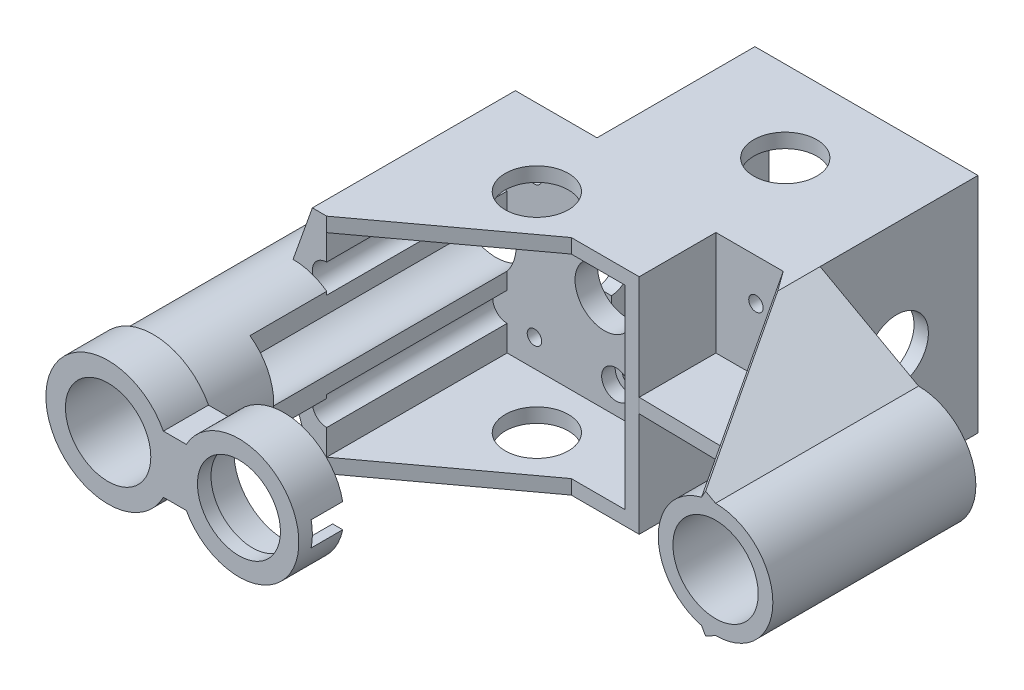
SolidWorks part; units mm, degrees
ref_plane "Front" through (0, 0, 0) normal (0, 0, 1) x (1, 0, 0)
ref_plane "Top" through (0, 0, 0) normal (0, 1, 0) x (1, 0, 0)
ref_plane "Right" through (0, 0, 0) normal (1, 0, 0) x (0, 0, -1)
sketch "Sketch4" plane through (0, 0, 0) normal (0, 0, 1) x (1, 0, 0)
  line L0 (0, -42.8625) -> (0, 41.275) construction
  line L1 (-49.15, -15.5) -> (-80.15, 15.5) construction
  line L2 (-80.15, -15.5) -> (-49.15, 15.5) construction
  line L3 (-39.925, 44.5615) -> (-39.925, -66.5635) construction
  line L4 (-71.275, 44.5615) -> (-71.275, -66.5635) construction
  line L8 (-62.05, 15.5) -> (-31.05, -15.5) construction
  line L9 (-31.05, 15.5) -> (-62.05, -15.5) construction
  line L11 (-31.05, 36.624) -> (-31.05, -53.8635) construction
  line L12 (43.75, 0) -> (-164.4633, 0) construction
  line L13 (-62.05, 36.624) -> (-62.05, -53.8635) construction
  line L14 (-49.15, 36.624) -> (-49.15, -53.8635) construction
  line L15 (-80.15, 36.624) -> (-80.15, -53.8635) construction
  line L16 (-113.2228, 15.5) -> (-0.2036, 15.5) construction
  line L17 (-113.2228, -15.5) -> (-0.2036, -15.5) construction
  line L18 (-25, -66.5635) -> (-25, 44.5615) construction
  line L19 (-68.1, -66.5635) -> (-68.1, 44.5615) construction
  line L20 (-43.1, 44.5615) -> (-43.1, -66.5635) construction
  line L21 (-86.2, -66.5635) -> (-86.2, 44.5615) construction
  line L22 (5.8397, -21.55) -> (-134.1626, -21.55) construction
  line L23 (5.8397, 21.55) -> (-134.1626, 21.55) construction
  line L24 (10.9249, -24.725) -> (-138.6228, -24.725) construction
  line L25 (10.9249, 24.725) -> (-138.6228, 24.725) construction
  line L26 (-89.375, 44.5615) -> (-89.375, -66.5635) construction
  line L27 (-21.825, 44.5615) -> (-21.825, -66.5635) construction
  circle A0 centre (0, 0) radius 12.7 construction
  circle A1 centre (0, 0) radius 15.875 construction
  circle A2 centre (0, 0) radius 9.46 construction
  circle A3 centre (-93.65, 0) radius 9.46 construction
  arc A4 (-93.65, 12.7) -> (-93.65, -12.7) centre (-93.65, 0) ccw construction
  circle A5 centre (27.27, 0) radius 9.46 construction
  circle A6 centre (27.27, 0) radius 12.7 construction
  circle A7 centre (-120.3675, 0) radius 9.46 construction
  circle A8 centre (-120.3675, 0) radius 12.7 construction
  point P3 (0, 0)
  point P6 (-49.15, -15.5)
  point P11 (-93.65, 0)
  point P12 (-49.15, 15.5)
  point P13 (-46.55, 0)
  point P14 (-80.15, 15.5)
  point P15 (-80.15, -15.5)
  point P61 (-64.65, 0)
  point P65 (27.27, 0)
  point P66 (-120.3675, 0)
  dimension "D20" = 3.175
  dimension "D18" = 29
  dimension "D26" = 73.82
  dimension "D27" = 64.65
  dimension "D2" = 31
  dimension "D3" = 25
  dimension "D4" = 31
  dimension "D5" = 21.825
  dimension "D6" = 15.5
  dimension "D7" = 15.5
  dimension "D8" = 6.05
  dimension "D9" = 6.05
  dimension "D10" = 6.05
  dimension "D11" = 6.05
  dimension "D12" = 6.05
  dimension "D13" = 6.05
  dimension "D14" = 3.175
  dimension "D15" = 3.175
  dimension "D16" = 3.175
  dimension "D17" = 3.175
  dimension "D19" = 3.175
  dimension "D21" = 3.175
  dimension "D22" = 46.55
  dimension "D23" = 47.1
  dimension "D24" = 58.32
  dimension "D25" = 147.6375
sketch "Sketch5" plane through (0, 0, 0) normal (0, 0, 1) x (1, 0, 0)
  line L0 (-21.825, -24.725) -> (0, -12.7)
  line L1 (10.9249, -24.725) -> (-138.6228, -24.725) construction
  line L2 (-21.825, 44.5615) -> (-21.825, -66.5635) construction
  line L3 (0, -42.8625) -> (0, 41.275) construction
  line L4 (10.9249, 24.725) -> (-138.6228, 24.725) construction
  line L5 (-21.825, 24.725) -> (0, 12.7)
  line L6 (-93.65, 0) -> (-93.65, -30.9694) construction
  line L7 (-93.65, 12.7) -> (-89.375, 24.725)
  line L8 (-89.375, 44.5615) -> (-89.375, -66.5635) construction
  line L9 (-89.375, 24.725) -> (-21.825, 24.725)
  line L10 (-89.375, -24.725) -> (-93.65, -12.7)
  line L11 (-89.375, -24.725) -> (-21.825, -24.725)
  circle A0 centre (0, 0) radius 12.7 construction
  arc A1 (0, 12.7) -> (0, -12.7) centre (0, 0) cw
  circle A2 centre (0, 0) radius 9.46
  circle A3 centre (-93.65, 0) radius 9.46
  arc A4 (-93.65, 12.7) -> (-93.65, -12.7) centre (-93.65, 0) ccw
  circle A6 centre (-31.05, 15.5) radius 1.6
  circle A7 centre (-31.05, -15.5) radius 1.6
  circle A8 centre (-49.15, -15.5) radius 1.6
  circle A9 centre (-49.15, 15.5) radius 1.6
  circle A10 centre (-62.05, 15.5) radius 1.6
  circle A11 centre (-80.15, 15.5) radius 1.6
  circle A12 centre (-80.15, -15.5) radius 1.6
  circle A13 centre (-62.05, -15.5) radius 1.6
extrude "Extrude1" add sketch "Sketch5" along normal blind 5
sketch "Sketch6" plane through (0, 0, 5) normal (0, 0, 1) x (1, 0, 0)
  line L0 (-86.2, -21.55) -> (-43.1, -21.55)
  line L1 (-86.2, -66.5635) -> (-86.2, 44.5615) construction
  line L2 (5.8397, -21.55) -> (-134.1626, -21.55) construction
  line L3 (-43.1, 44.5615) -> (-43.1, -66.5635) construction
  line L4 (-43.1, -21.55) -> (-43.1, 21.55)
  line L5 (5.8397, 21.55) -> (-134.1626, 21.55) construction
  line L6 (-43.1, 21.55) -> (-86.2, 21.55)
  line L7 (-39.925, 24.725) -> (-89.375, 24.725)
  line L8 (-93.65, -12.7) -> (-89.375, -24.725) construction
  line L9 (-39.925, 44.5615) -> (-39.925, -66.5635) construction
  line L10 (10.9249, 24.725) -> (-138.6228, 24.725) construction
  line L11 (-12.601, 1.5825) -> (-39.925, 1.5825)
  line L12 (-39.925, -24.725) -> (-89.375, -24.725)
  line L13 (-86.2, 21.55) -> (-86.2, 15.8916)
  line L14 (-86.2, -9.5084) -> (-86.2, -5.83)
  line L15 (-89.375, -24.725) -> (-93.65, -12.7)
  line L16 (-89.375, 24.725) -> (-93.65, 12.7)
  line L19 (-86.2, 9.5416) -> (-86.2, 5.83)
  line L20 (-86.2, -21.55) -> (-86.2, -15.8584)
  line L24 (-39.925, -1.5851) -> (-12.6007, -1.5851)
  line L25 (-39.925, 1.5825) -> (-39.925, 24.725)
  line L27 (-21.825, -24.725) -> (0, -12.7)
  line L28 (-21.825, 24.725) -> (0, 12.7)
  line L29 (-25, 24.725) -> (-3.1127, 12.3127)
  line L30 (-25, -66.5635) -> (-25, 44.5615) construction
  line L31 (-25, -24.725) -> (-3.1127, -12.3127)
  line L32 (10.9249, -24.725) -> (-138.6228, -24.725) construction
  line L33 (-25, -24.725) -> (-21.825, -24.725)
  line L34 (-39.925, -1.5851) -> (-39.925, -24.725)
  line L35 (-25, 24.725) -> (-21.825, 24.725)
  line L36 (0, -42.8625) -> (0, 41.275) construction
  circle A0 centre (-93.65, 0) radius 9.46 construction
  arc A1 (-93.65, 12.7) -> (-93.65, -12.7) centre (-93.65, 0) ccw
  arc A3 (-86.2, 5.83) -> (-86.2, -5.83) centre (-93.65, 0) ccw
  circle A4 centre (0, 0) radius 9.46
  circle A5 centre (0, 0) radius 12.7 construction
  arc A6 (0, -12.7) -> (0, 12.7) centre (0, 0) ccw
  arc A7 (-3.1127, 12.3127) -> (-12.601, 1.5825) centre (0, 0) ccw
  arc A8 (-3.1127, -12.3127) -> (-12.6007, -1.5851) centre (0, 0) cw
  circle A13 centre (-86.2, 12.7166) radius 3.175 construction
  circle A14 centre (-86.2, -12.6834) radius 3.175 construction
  arc A15 (-86.2, 15.8916) -> (-86.2, 9.5416) centre (-86.2, 12.7166) ccw
  arc A16 (-86.2, -9.5084) -> (-86.2, -15.8584) centre (-86.2, -12.6834) ccw
  point P36 (-86.2, 12.7166)
  point P39 (-86.2, -12.6834)
extrude "Extrude2" add sketch "Sketch6" along normal blind 40
sketch "Sketch7" plane through (0, 0, 0) normal (0, 0, -1) x (-1, 0, 0)
  line L0 (68.1, 21.55) -> (25, 21.55)
  line L1 (25, -66.5635) -> (25, 44.5615) construction
  line L2 (-5.8397, -21.55) -> (134.1626, -21.55) construction
  line L3 (25, 21.55) -> (25, -21.55)
  line L4 (68.1, -66.5635) -> (68.1, 44.5615) construction
  line L5 (-5.8397, 21.55) -> (134.1626, 21.55) construction
  line L6 (68.1, 21.55) -> (68.1, -21.55)
  line L7 (68.1, -21.55) -> (25, -21.55)
  line L8 (21.825, 24.725) -> (21.825, -24.725)
  line L9 (21.825, 24.725) -> (71.275, 24.725)
  line L10 (71.275, 44.5615) -> (71.275, -66.5635) construction
  line L11 (-10.9249, 24.725) -> (138.6228, 24.725) construction
  line L12 (71.275, 24.725) -> (71.275, -24.725)
  line L13 (-10.9249, -24.725) -> (138.6228, -24.725) construction
  line L14 (71.275, -24.725) -> (21.825, -24.725)
extrude "Extrude3" add sketch "Sketch7" along normal blind 35
sketch "Sketch12" plane through (4.5259, 7.9808, 0) normal (-0.4933, -0.8699, 0) x (0, 0, 1)
  line L0 (45, 8.7814) -> (5, 33.9433)
  line L1 (5, 33.9433) -> (45, 33.9433)
  line L2 (45, 33.9433) -> (45, 8.7814)
extrude "Extrude5" cut sketch "Sketch12" against normal up to surface (1.5323 mm away) up to face at (-10.9125, 18.7125, 22.5)
sketch "Sketch13" plane through (4.5259, -7.9808, 0) normal (-0.4933, 0.8699, 0) x (0, 0, 1)
  line L0 (45, -8.7814) -> (5, -33.9433)
  line L1 (5, -33.9433) -> (45, -33.9433)
  line L2 (45, -33.9433) -> (45, -8.7814)
extrude "Extrude6" cut sketch "Sketch13" against normal up to surface (1.5323 mm away) up to face at (-10.9125, -18.7125, 22.5)
sketch "Sketch16" plane through (0, -24.725, 0) normal (0, -1, 0) x (1, 0, 0)
  line L0 (-39.925, 5) -> (-39.925, 22) construction
  line L1 (-39.925, 45) -> (-39.925, 5) construction
  line L2 (-39.925, 22) -> (-16.782, 22.4034)
  line L3 (-16.782, 22.4034) -> (-12.6007, 29.0539)
  line L4 (-12.6007, 45) -> (-12.6007, 5) construction
  line L5 (-12.6007, 29.0539) -> (-12.6007, 45)
  line L6 (-12.6007, 45) -> (-86.2, 45)
  line L7 (-86.2, 45) -> (-54.9816, 22)
  line L8 (-54.9816, 22) -> (-39.925, 22)
  line L9 (-46.55, 0) -> (-46.55, -39.1338) construction
  line L10 (-67.6181, 0) -> (-67.6181, 27.6964) construction
  line L11 (10.9249, 0) -> (-138.6228, 0) construction
  circle A0 centre (-46.55, -17) radius 7
  circle A1 centre (-67.6181, 17) radius 7
extrude "Extrude9" cut sketch "Sketch16" against normal up to surface (49.45 mm away) up to face at (-47.67, 24.725, 3.9695)
sketch "Sketch17" plane through (0, 0, 45) normal (0, 0, 1) x (1, 0, 0)
  line L1 (-86.2, -66.5635) -> (-86.2, 44.5615) construction
  line L2 (-86.2, 10.2853) -> (-86.2, 5.83)
  line L3 (-86.2, -5.83) -> (-86.2, -10.2853)
  arc A0 (-86.2, 5.83) -> (-86.2, -5.83) centre (-93.65, 0) ccw
  arc A1 (-93.65, 12.7) -> (-92.406, -12.6389) centre (-93.65, 0) ccw
  arc A2 (-93.65, 12.7) -> (-93.65, -12.7) centre (-93.65, 0) ccw construction
  arc A3 (-92.406, -12.6389) -> (-86.2, -10.2853) centre (-93.65, 0) ccw
  arc A4 (-93.65, 12.7) -> (-86.2, 10.2853) centre (-93.65, 0) cw
extrude "Extrude10" add sketch "Sketch17" along normal blind 17
sketch "Sketch18" plane through (0, 0, 62) normal (0, 0, 1) x (1, 0, 0)
  circle A0 centre (-93.65, 0) radius 9.46
  circle A1 centre (-93.65, 0) radius 12.7
extrude "Extrude11" add sketch "Sketch18" along normal blind 14
sketch "Sketch19" plane through (0, 0, 76) normal (0, 0, 1) x (1, 0, 0)
  line L0 (-81.3983, -6.3446) -> (-76.3158, -6.3446)
  line L1 (-81.3983, 6.3446) -> (-76.3158, 6.3446)
  circle A0 centre (-64.65, 0) radius 11.1
  circle A1 centre (-64.65, 0) radius 13.2795 construction
  circle A2 centre (-93.65, 0) radius 9.46
  circle A3 centre (-93.65, 0) radius 13.797 construction
  arc A4 (-76.3158, -6.3446) -> (-76.3158, 6.3446) centre (-64.65, 0) ccw
  arc A5 (-81.3983, 6.3446) -> (-81.3983, -6.3446) centre (-93.65, 0) ccw
extrude "Extrude12" add sketch "Sketch19" along normal blind 7
sketch "Sketch20" plane through (0, 0, 83) normal (0, 0, 1) x (1, 0, 0)
  line L1 (-81.3983, -6.3446) -> (-76.3158, -6.3446) construction
  line L2 (-81.3983, -6.3446) -> (-76.3158, -6.3446)
  line L3 (-81.3983, 6.3446) -> (-76.3158, 6.3446)
  circle A0 centre (-93.65, 0) radius 9.46
  circle A1 centre (-93.65, 0) radius 12.7 construction
  circle A2 centre (-64.65, 0) radius 14.39 construction
  arc A3 (-81.3983, 6.3446) -> (-81.3983, -6.3446) centre (-93.65, 0) ccw
  arc A4 (-76.3158, -6.3446) -> (-76.3158, 6.3446) centre (-64.65, 0) ccw
  circle A5 centre (-64.65, 0) radius 9.2
extrude "Extrude13" add sketch "Sketch20" along normal blind 3
sketch "Sketch21" plane through (-43.1, 0, 0) normal (-1, 0, 0) x (0, 0, 1)
  line L0 (76, 0) -> (76, -2.7)
  line L1 (76, 13.797) -> (76, -13.797) construction
  line L2 (76, 0) -> (76, 2.7)
  line L3 (76, -2.7) -> (83, -2.7)
  line L4 (83, 11.1) -> (83, -11.1) construction
  line L5 (83, -2.7) -> (83, 2.7)
  line L6 (83, 2.7) -> (76, 2.7)
extrude "Extrude14" cut sketch "Sketch21" along normal blind 15
sketch "Sketch22" plane through (0, 0, 5) normal (0, 0, 1) x (1, 0, 0)
  circle A0 centre (-62.05, 15.5) radius 3.2
  circle A1 centre (-62.05, -15.5) radius 3.2
extrude "Extrude15" cut sketch "Sketch22" against normal blind 3
sketch "Sketch23" plane through (0, 0, 0) normal (0, 0, -1) x (-1, 0, 0)
  circle A0 centre (49.15, 15.5) radius 3.2
  circle A1 centre (49.15, -15.5) radius 3.2
extrude "Extrude16" cut sketch "Sketch23" against normal blind 3
sketch "Sketch24" plane through (-71.275, 0, 0) normal (-1, 0, 0) x (0, 0, 1)
  line L0 (0, 0) -> (0, 4)
  line L1 (0, -66.5635) -> (0, 44.5615) construction
  line L2 (0, 0) -> (0, -4)
  circle A0 centre (-17, 0) radius 7
  arc A1 (0, 4) -> (0, -4) centre (0, 0) ccw
extrude "Extrude17" cut sketch "Sketch24" against normal up to surface (49.45 mm away) up to face at (-21.825, 0, -17.5)
sketch "Sketch25" plane through (0, 0, 0) normal (0, 0, -1) x (-1, 0, 0)
  circle A0 centre (46.55, 0) radius 6.5
  circle A1 centre (64.65, 0) radius 6.5
extrude "Extrude18" cut sketch "Sketch25" against normal up to surface (5 mm away) up to face at (-58.85, -15.5, 5)
